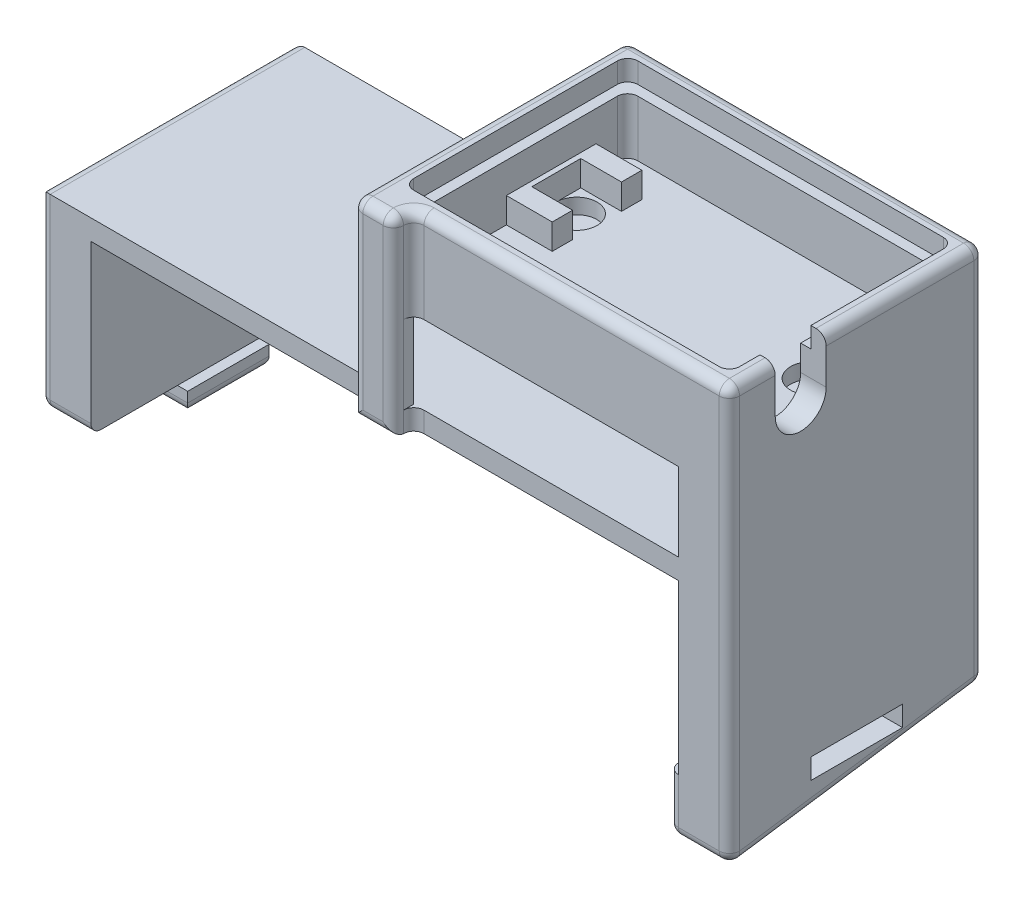
SolidWorks part; units mm, degrees
ref_plane "Front Plane" through (0, 0, 0) normal (0, 0, 1) x (1, 0, 0)
ref_plane "Top Plane" through (0, 0, 0) normal (0, 1, 0) x (1, 0, 0)
ref_plane "Right Plane" through (0, 0, 0) normal (1, 0, 0) x (0, 0, -1)
sketch "Sketch1" plane through (0, 0, 0) normal (0, 0, 1) x (1, 0, 0)
  line L0 (0, 0) -> (30, 0)
  line L1 (30, 0) -> (30, -7.7)
  line L2 (30, -7.7) -> (-32.7, -7.7)
  line L3 (-32.7, -7.7) -> (-32.7, -26.2)
  line L4 (-32.7, -26.2) -> (35, -26.2)
  line L5 (35, -26.2) -> (35, 9)
  line L6 (35, 9) -> (0, 9)
  line L7 (0, 9) -> (0, 0)
  dimension "D1" = 7.7
  dimension "D2" = 30
  dimension "D3" = 35
  dimension "D4" = 67.7
  dimension "D5" = 9
  dimension "D6" = 18.5
extrude "Boss-Extrude1" add sketch "Sketch1" along normal blind 25
sketch "Sketch2" plane through (0, 0, 25) normal (0, 0, 1) x (1, 0, 0)
  line L0 (-32.7, -26.2) -> (35, -26.2) construction
  line L1 (30, -26.2) -> (-27.7, -26.2)
  line L2 (30, -26.2) -> (30, -9.7)
  line L3 (30, -9.7) -> (-27.7, -9.7)
  line L4 (-27.7, -26.2) -> (-27.7, -9.7)
  line L5 (35, -26.2) -> (35, 9) construction
  dimension "D1" = 57.7
  dimension "D2" = 5
  dimension "D3" = 16.5
extrude "Cut-Extrude1" cut sketch "Sketch2" against normal through all
sketch "Sketch3" plane through (0, 9, 0) normal (0, 1, 0) x (1, 0, 0)
  line L0 (35, -25) -> (35, 0) construction
  line L1 (2.5, -2.5) -> (32.5, -2.5)
  line L2 (2.5, -2.5) -> (2.5, -22.5)
  line L3 (2.5, -22.5) -> (32.5, -22.5)
  line L4 (32.5, -2.5) -> (32.5, -22.5)
  line L5 (0, -25) -> (0, 0) construction
  line L6 (35, 0) -> (0, 0) construction
  line L7 (35, -25) -> (0, -25) construction
  dimension "D1" = 2.5
  dimension "D2" = 2.5
  dimension "D3" = 2.5
  dimension "D4" = 2.5
extrude "Cut-Extrude2" cut sketch "Sketch3" against normal blind 7.5
sketch "Sketch4" plane through (0, -26.2, 0) normal (0, -1, 0) x (1, 0, 0)
  line L0 (35, 12.5) -> (35.1733, 12.5) construction
  line L1 (35, 25) -> (35, 0) construction
  line L2 (30, 0) -> (30, 25) construction
  circle A0 centre (30.5, 12.5) radius 2
  dimension "D1" = 4
  dimension "D2" = 0.5
extrude "Cut-Extrude3" cut sketch "Sketch4" against normal up to surface (27.7 mm away) up to face at (17.5, 1.5, 12.5)
sketch "Sketch5" plane through (0, 1.5, 0) normal (0, 1, 0) x (1, 0, 0)
  line L0 (35, -25) -> (0, -25) construction
  line L2 (30, -25) -> (30, -14.4365) construction
  circle A0 centre (5, -10) radius 2
  dimension "D1" = 4
  dimension "D2" = 25
  dimension "D3" = 15
extrude "Cut-Extrude4" cut sketch "Sketch5" against normal up to surface (1.5 mm away) up to face at (19.75, 0, 12.5)
sketch "Sketch6" plane through (0, -26.2, 0) normal (0, -1, 0) x (1, 0, 0)
  line L0 (35, 25) -> (35, 0) construction
  line L1 (35, 25) -> (29, 25)
  line L2 (35, 25) -> (35, 17)
  line L3 (35, 17) -> (29, 17)
  line L4 (29, 25) -> (29, 17)
  line L5 (35, 0) -> (29, 0)
  line L6 (35, 0) -> (35, 8)
  line L7 (35, 8) -> (29, 8)
  line L8 (29, 0) -> (29, 8)
  line L9 (-32.7, 25) -> (-32.7, 0) construction
  line L10 (-32.7, 16.5) -> (-26.7, 16.5)
  line L11 (-32.7, 16.5) -> (-32.7, 8.5)
  line L12 (-32.7, 8.5) -> (-26.7, 8.5)
  line L13 (-26.7, 16.5) -> (-26.7, 8.5)
  line L14 (35, 12.5) -> (36.5966, 12.5) construction
  dimension "D1" = 8
  dimension "D2" = 6
extrude "Boss-Extrude2" add sketch "Sketch6" along normal blind 2
sketch "Sketch7" plane through (0, 0, 25) normal (0, 0, 1) x (1, 0, 0)
  line L0 (0, 9) -> (0, -9.7)
  line L1 (35, 9) -> (0, 9) construction
  line L3 (30, -9.7) -> (-27.7, -9.7) construction
  line L4 (4, -9.7) -> (4, 9)
  line L5 (4, 9) -> (0, 9)
  line L20 (30, -9.7) -> (30, -26.2)
  line L21 (30, -26.2) -> (29, -26.2)
  line L22 (29, -26.2) -> (29, -28.2)
  line L23 (29, -28.2) -> (35, -28.2)
  line L24 (35, -28.2) -> (35, 9)
  line L25 (35, 9) -> (0, 9)
  line L26 (0, 9) -> (0, 0)
  line L27 (0, 0) -> (30, 0)
  line L28 (30, 0) -> (30, -7.7)
  line L29 (30, -7.7) -> (-32.7, -7.7)
  line L30 (-32.7, -7.7) -> (-32.7, -26.2)
  line L31 (-32.7, -26.2) -> (-27.7, -26.2)
  line L32 (-27.7, -26.2) -> (-27.7, -9.7)
  line L33 (-27.7, -9.7) -> (30, -9.7)
  line L47 (0, -9.7) -> (4, -9.7)
  dimension "D2" = 4
  dimension "D1" = 0
extrude "Boss-Extrude3" add sketch "Sketch7" along normal blind 2
sketch "Sketch8" plane through (35, 0, 0) normal (1, 0, 0) x (0, 0, -1)
  line L0 (0, -28.2) -> (-25, -31.8607)
  line L2 (-25, -31.8607) -> (-25, -28.2)
  line L3 (-25, -28.2) -> (-25, 9) construction
  line L4 (-25, -28.2) -> (0, -28.2)
  line L5 (0, -28.2) -> (-8, -28.2) construction
  dimension "D1" = 8.331
  dimension "D2" = 3.6607
extrude "Boss-Extrude4" add sketch "Sketch8" against normal up to surface (6 mm away) up to face at (29, -27.2, 4)
sketch "Sketch9" plane through (0, 9, 0) normal (0, 1, 0) x (1, 0, 0)
  line L0 (32.5, -22.5) -> (32.5, -2.5) construction
  line L1 (33.5, -23.5) -> (1.5, -23.5)
  line L2 (33.5, -23.5) -> (33.5, -1.5)
  line L3 (33.5, -1.5) -> (1.5, -1.5)
  line L4 (1.5, -23.5) -> (1.5, -1.5)
  line L5 (2.5, -22.5) -> (32.5, -22.5) construction
  line L6 (2.5, -2.5) -> (2.5, -22.5) construction
  line L7 (32.5, -2.5) -> (2.5, -2.5) construction
  dimension "D1" = 1
  dimension "D2" = 1
  dimension "D3" = 1
  dimension "D4" = 1
extrude "Cut-Extrude5" cut sketch "Sketch9" against normal blind 2
fillet "Fillet1" radius 1 8 edges at (33.5, 8, 1.5) (1.5, 8, 1.5) (1.5, 8, 23.5) (33.5, 8, 23.5) (32.5, 4.25, 2.5) (2.5, 4.25, 2.5) (2.5, 4.25, 22.5) (32.5, 4.25, 22.5)
fillet "Fillet2" radius 1 34 edges at (0, 9, 13.5) (17.5, 9, 0) (35, 9, 12.5) (29, -29.0304, 25) (29, -27.2, 0) (29, -30.0304, 12.5) (35, -30.0304, 12.5) (-30.2, -26.2, 0) (-30.2, -26.2, 25) (-29.7, -28.2, 8.5) (-29.7, -28.2, 16.5) (-32.7, -27.2, 8.5) (-32.7, -27.2, 16.5) (-32.7, -26.2, 20.75) (-32.7, -28.2, 12.5) (-32.7, -26.2, 4.25) (-32.7, -7.7, 12.5) (-32.7, -16.95, 0) (-32.7, -16.95, 25) (35, -9.6, 0) (35, -11.4304, 25) (0, -0.35, 27) (0, 4.5, 0) (4, -0.35, 27) (2, -9.7, 27) (2, 9, 27) (32, -31.8607, 25) (32, -28.2, 0) (-26.7, -28.2, 12.5)
sketch "Sketch10" plane through (-27.7, 0, 0) normal (1, 0, 0) x (0, 0, -1)
  line L0 (-12.5, -9.7) -> (-12.5, -2.753) construction
  line L1 (0, -9.7) -> (-25, -9.7) construction
  circle A0 centre (-14, -12.05) radius 1
  circle A1 centre (-11, -12.05) radius 1
  dimension "D2" = 2
  dimension "D3" = 2
  dimension "D1" = 3
  dimension "D4" = 2.35
extrude "Boss-Extrude5" add sketch "Sketch10" along normal blind 1.5
fillet "Fillet3" radius 1 2 edges at (-26.2, -12.05, 13) (-26.2, -12.05, 10)
sketch "Sketch11" plane through (0, 1.5, 0) normal (0, 1, 0) x (1, 0, 0)
  line L0 (2.5, -5.6) -> (2.5, -14.4)
  line L1 (2.5, -21.5) -> (2.5, -3.5) construction
  line L2 (2.5, -14.4) -> (7, -14.4)
  line L3 (7, -14.4) -> (7, -12.4)
  line L4 (7, -12.4) -> (3, -12.4)
  line L5 (3, -12.4) -> (3, -7.6)
  line L6 (3, -7.6) -> (7, -7.6)
  line L7 (7, -7.6) -> (7, -5.6)
  line L8 (7, -5.6) -> (2.5, -5.6)
  line L9 (5, -10) -> (10.1114, -10) construction
  dimension "D1" = 2
  dimension "D2" = 2
  dimension "D3" = 0.5
  dimension "D4" = 4.5
  dimension "D5" = 4.8
extrude "Boss-Extrude6" add sketch "Sketch11" along normal blind 2.5
sketch "Sketch12" plane through (35, 0, 0) normal (1, 0, 0) x (0, 0, -1)
  line L0 (-20.5, 9) -> (-20.5, 4.5)
  line L1 (-24, 9) -> (-1, 9) construction
  line L2 (-15.5, 4.5) -> (-15.5, 9)
  line L3 (-15.5, 9) -> (-20.5, 9)
  line L4 (-25, 8) -> (-25, 0) construction
  arc A0 (-20.5, 4.5) -> (-15.5, 4.5) centre (-18, 4.5) ccw
  dimension "D1" = 2.5
  dimension "D2" = 4.5
  dimension "D3" = 7
extrude "Cut-Extrude6" cut sketch "Sketch12" against normal up to surface (2.5 mm away) up to face at (32.5, 3.7, 12.5)
